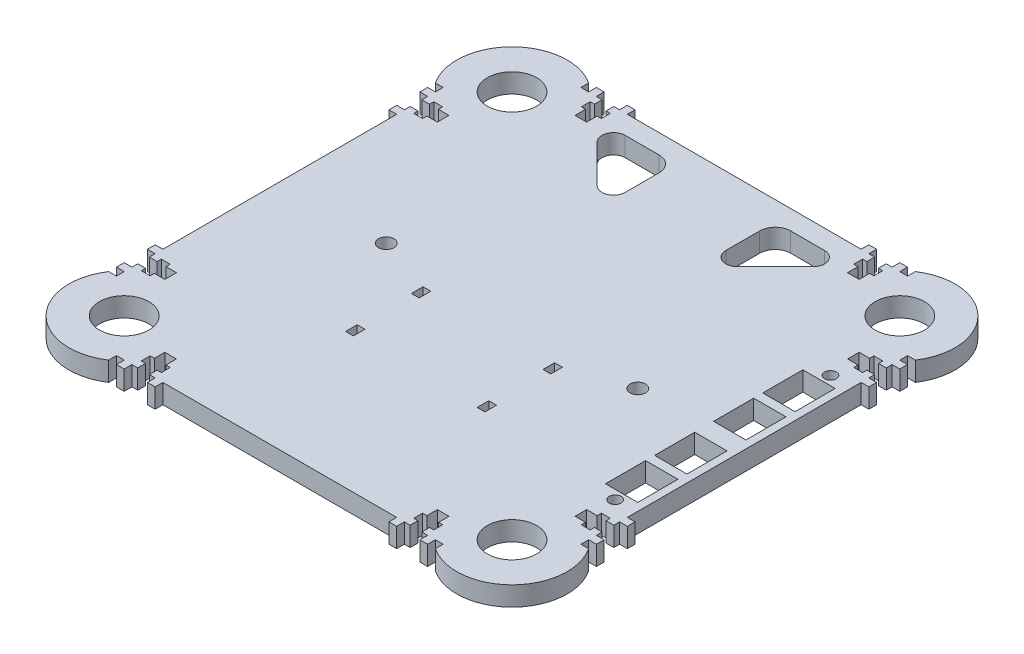
SolidWorks part; units mm, degrees
ref_plane "Front Plane" through (0, 0, 0) normal (0, 0, 1) x (1, 0, 0)
ref_plane "Top Plane" through (0, 0, 0) normal (0, 1, 0) x (1, 0, 0)
ref_plane "Right Plane" through (0, 0, 0) normal (1, 0, 0) x (0, 0, -1)
sketch "Sketch1" plane through (0, 0, 0) normal (0, 1, 0) x (1, 0, 0)
  line L1 (0, 0) -> (120, 0)
  line L2 (0, 0) -> (0, 120)
  line L3 (0, 120) -> (120, 120)
  line L4 (120, 0) -> (120, 120)
  dimension "D1" = 120
  dimension "D2" = 120
extrude "Boss-Extrude1" add sketch "Sketch1" along normal blind 5
sketch "Sketch2" plane through (0, 5, 0) normal (0, 1, 0) x (1, 0, 0)
  line L0 (60, 120) -> (60, 0) construction
  line L1 (120, 120) -> (0, 120) construction
  line L2 (0, 0) -> (120, 0) construction
  line L3 (120, 60) -> (0, 60) construction
  line L4 (120, 0) -> (120, 120) construction
  line L5 (0, 120) -> (0, 0) construction
  line L6 (60, 60) -> (120, 120) construction
  line L7 (110.1005, 110.1005) -> (120, 100.201) construction
  line L8 (110.1005, 110.1005) -> (100.201, 120) construction
  line L9 (100.201, 120) -> (120, 100.201)
  line L10 (100.201, 120) -> (114.3431, 134.1421)
  line L11 (120, 100.201) -> (134.1421, 114.3431)
  line L12 (114.3431, 134.1421) -> (134.1421, 114.3431)
  line L13 (0, 100.201) -> (-14.1421, 114.3431)
  line L14 (5.6569, 134.1421) -> (-14.1421, 114.3431)
  line L15 (19.799, 120) -> (5.6569, 134.1421)
  line L16 (19.799, 120) -> (0, 100.201)
  line L17 (19.799, 0) -> (0, 19.799)
  line L18 (19.799, 0) -> (5.6569, -14.1421)
  line L19 (5.6569, -14.1421) -> (-14.1421, 5.6569)
  line L20 (0, 19.799) -> (-14.1421, 5.6569)
  line L21 (120, 19.799) -> (134.1421, 5.6569)
  line L22 (114.3431, -14.1421) -> (134.1421, 5.6569)
  line L23 (100.201, 0) -> (114.3431, -14.1421)
  line L24 (100.201, 0) -> (120, 19.799)
  point P33 (120, 100.201)
  point P34 (100.201, 120)
  dimension "D1" = 28
  dimension "D2" = 20
extrude "Boss-Extrude3" add sketch "Sketch2" against normal blind 5
sketch "Sketch3" plane through (0, 5, 0) normal (0, 1, 0) x (1, 0, 0)
  line L0 (-4.2426, -4.2426) -> (124.2426, 124.2426) construction
  line L1 (-14.1421, 5.6569) -> (5.6569, -14.1421) construction
  line L2 (134.1421, 114.3431) -> (114.3431, 134.1421) construction
  line L3 (0, 19.799) -> (19.799, 0) construction
  line L13 (0, 60) -> (120, 60) construction
  line L14 (0, 100.201) -> (0, 19.799) construction
  line L15 (120, 19.799) -> (120, 100.201) construction
  line L16 (60, 0) -> (60, 120) construction
  line L17 (19.799, 0) -> (100.201, 0) construction
  line L18 (100.201, 120) -> (19.799, 120) construction
  circle A16 centre (9.8995, 9.8995) radius 6.375
  circle A17 centre (110.1005, 9.8995) radius 6.375
  circle A18 centre (9.8995, 110.1005) radius 6.375
  circle A19 centre (110.1005, 110.1005) radius 6.375
  point P10 (9.8995, 9.8995)
  dimension "D1" = 12.75
extrude "Cut-Extrude1" cut sketch "Sketch3" against normal blind 5
sketch "Sketch6" plane through (0, 5, 0) normal (0, 1, 0) x (1, 0, 0)
  line L0 (0, 19.799) -> (0, 17.799)
  line L1 (0, 17.799) -> (-2, 17.799)
  line L2 (0, 19.799) -> (-14.1421, 5.6569) construction
  line L3 (-2, 17.799) -> (0, 19.799)
  line L4 (0, 0) -> (124.2426, 124.2426) construction
  line L5 (134.1421, 114.3431) -> (114.3431, 134.1421) construction
  line L6 (60, 120) -> (60, 0) construction
  line L7 (100.201, 120) -> (19.799, 120) construction
  line L8 (19.799, 0) -> (100.201, 0) construction
  line L9 (0, 60) -> (120, 60) construction
  line L10 (0, 100.201) -> (0, 19.799) construction
  line L11 (120, 19.799) -> (120, 100.201) construction
  line L12 (17.799, -2) -> (19.799, 0)
  line L13 (17.799, 0) -> (17.799, -2)
  line L14 (19.799, 0) -> (17.799, 0)
  line L15 (100.201, 0) -> (102.201, 0)
  line L16 (102.201, 0) -> (102.201, -2)
  line L17 (102.201, -2) -> (100.201, 0)
  line L18 (122, 17.799) -> (120, 19.799)
  line L19 (120, 17.799) -> (122, 17.799)
  line L20 (120, 19.799) -> (120, 17.799)
  line L21 (120, 100.201) -> (120, 102.201)
  line L22 (120, 102.201) -> (122, 102.201)
  line L23 (122, 102.201) -> (120, 100.201)
  line L24 (102.201, 122) -> (100.201, 120)
  line L25 (102.201, 120) -> (102.201, 122)
  line L26 (100.201, 120) -> (102.201, 120)
  line L27 (19.799, 120) -> (17.799, 120)
  line L28 (17.799, 120) -> (17.799, 122)
  line L29 (17.799, 122) -> (19.799, 120)
  line L30 (-2, 102.201) -> (0, 100.201)
  line L31 (0, 102.201) -> (-2, 102.201)
  line L32 (0, 100.201) -> (0, 102.201)
  dimension "D1" = 2
extrude "Cut-Extrude4" cut sketch "Sketch6" against normal blind 10
sketch "Sketch8" plane through (0, 5, 0) normal (0, 1, 0) x (1, 0, 0)
  line L0 (60, 0) -> (60, 120) construction
  line L1 (17.799, 0) -> (102.201, 0) construction
  line L2 (102.201, 120) -> (17.799, 120) construction
  line L3 (0, 60) -> (120, 60) construction
  line L4 (0, 102.201) -> (0, 17.799) construction
  line L5 (120, 17.799) -> (120, 102.201) construction
  line L6 (-4.2426, 124.2426) -> (124.2426, -4.2426) construction
  line L7 (5.6569, 134.1421) -> (-14.1421, 114.3431) construction
  line L8 (114.3431, -14.1421) -> (134.1421, 5.6569) construction
  line L9 (24.799, 0) -> (24.799, 7) construction
  line L10 (23.299, 2) -> (23.299, 0)
  line L11 (26.299, 7) -> (23.299, 7)
  line L12 (26.299, 7) -> (26.299, 4.3)
  line L13 (26.299, 0) -> (23.299, 0)
  line L14 (23.299, 7) -> (23.299, 4.3)
  line L15 (26.299, 7) -> (23.299, 0) construction
  line L16 (26.299, 0) -> (23.299, 7) construction
  line L17 (23.299, 2) -> (22.199, 2)
  line L19 (23.299, 4.3) -> (22.199, 4.3)
  line L20 (22.199, 2) -> (22.199, 4.3)
  line L21 (26.299, 4.3) -> (27.399, 4.3)
  line L22 (27.399, 2) -> (27.399, 4.3)
  line L23 (26.299, 2) -> (27.399, 2)
  line L24 (26.299, 2) -> (26.299, 0)
  line L25 (17.799, 0) -> (17.799, -2) construction
  line L26 (93.701, 0) -> (96.701, 7) construction
  line L27 (93.701, 7) -> (96.701, 0) construction
  line L28 (95.201, 0) -> (95.201, 7) construction
  line L29 (93.701, 2) -> (93.701, 0)
  line L30 (93.701, 2) -> (92.601, 2)
  line L31 (92.601, 2) -> (92.601, 4.3)
  line L32 (93.701, 4.3) -> (92.601, 4.3)
  line L33 (97.801, 2) -> (97.801, 4.3)
  line L34 (96.701, 4.3) -> (97.801, 4.3)
  line L35 (96.701, 2) -> (97.801, 2)
  line L36 (96.701, 7) -> (96.701, 4.3)
  line L37 (93.701, 0) -> (96.701, 0)
  line L38 (93.701, 7) -> (93.701, 4.3)
  line L39 (93.701, 7) -> (96.701, 7)
  line L40 (96.701, 2) -> (96.701, 0)
  line L41 (95.201, 120) -> (95.201, 113) construction
  line L42 (93.701, 113) -> (96.701, 120) construction
  line L43 (93.701, 120) -> (96.701, 113) construction
  line L44 (26.299, 120) -> (23.299, 113) construction
  line L45 (26.299, 113) -> (23.299, 120) construction
  line L46 (24.799, 120) -> (24.799, 113) construction
  line L47 (96.701, 118) -> (96.701, 120)
  line L48 (93.701, 113) -> (96.701, 113)
  line L49 (93.701, 113) -> (93.701, 115.7)
  line L50 (93.701, 120) -> (96.701, 120)
  line L51 (96.701, 113) -> (96.701, 115.7)
  line L52 (96.701, 118) -> (97.801, 118)
  line L53 (96.701, 115.7) -> (97.801, 115.7)
  line L54 (97.801, 118) -> (97.801, 115.7)
  line L55 (93.701, 115.7) -> (92.601, 115.7)
  line L56 (92.601, 118) -> (92.601, 115.7)
  line L57 (93.701, 118) -> (92.601, 118)
  line L58 (93.701, 118) -> (93.701, 120)
  line L59 (26.299, 118) -> (26.299, 120)
  line L60 (26.299, 118) -> (27.399, 118)
  line L61 (27.399, 118) -> (27.399, 115.7)
  line L62 (26.299, 115.7) -> (27.399, 115.7)
  line L63 (22.199, 118) -> (22.199, 115.7)
  line L64 (23.299, 115.7) -> (22.199, 115.7)
  line L65 (23.299, 118) -> (22.199, 118)
  line L66 (23.299, 113) -> (23.299, 115.7)
  line L67 (26.299, 120) -> (23.299, 120)
  line L68 (26.299, 113) -> (26.299, 115.7)
  line L69 (26.299, 113) -> (23.299, 113)
  line L70 (23.299, 118) -> (23.299, 120)
  line L71 (0, 95.201) -> (7, 95.201) construction
  line L72 (7, 93.701) -> (0, 96.701) construction
  line L73 (0, 93.701) -> (7, 96.701) construction
  line L74 (0, 26.299) -> (7, 23.299) construction
  line L75 (7, 26.299) -> (0, 23.299) construction
  line L76 (0, 24.799) -> (7, 24.799) construction
  line L77 (120, 24.799) -> (113, 24.799) construction
  line L78 (113, 26.299) -> (120, 23.299) construction
  line L79 (120, 26.299) -> (113, 23.299) construction
  line L80 (120, 93.701) -> (113, 96.701) construction
  line L81 (113, 93.701) -> (120, 96.701) construction
  line L82 (120, 95.201) -> (113, 95.201) construction
  line L83 (2, 96.701) -> (0, 96.701)
  line L84 (7, 93.701) -> (7, 96.701)
  line L85 (7, 93.701) -> (4.3, 93.701)
  line L86 (0, 93.701) -> (0, 96.701)
  line L87 (7, 96.701) -> (4.3, 96.701)
  line L88 (2, 96.701) -> (2, 97.801)
  line L89 (4.3, 96.701) -> (4.3, 97.801)
  line L90 (2, 97.801) -> (4.3, 97.801)
  line L91 (4.3, 93.701) -> (4.3, 92.601)
  line L92 (2, 92.601) -> (4.3, 92.601)
  line L93 (2, 93.701) -> (2, 92.601)
  line L94 (2, 93.701) -> (0, 93.701)
  line L95 (2, 26.299) -> (0, 26.299)
  line L96 (2, 26.299) -> (2, 27.399)
  line L97 (2, 27.399) -> (4.3, 27.399)
  line L98 (4.3, 26.299) -> (4.3, 27.399)
  line L99 (2, 22.199) -> (4.3, 22.199)
  line L100 (4.3, 23.299) -> (4.3, 22.199)
  line L101 (2, 23.299) -> (2, 22.199)
  line L102 (7, 23.299) -> (4.3, 23.299)
  line L103 (0, 26.299) -> (0, 23.299)
  line L104 (7, 26.299) -> (4.3, 26.299)
  line L105 (7, 26.299) -> (7, 23.299)
  line L106 (2, 23.299) -> (0, 23.299)
  line L107 (118, 23.299) -> (120, 23.299)
  line L108 (113, 26.299) -> (113, 23.299)
  line L109 (113, 26.299) -> (115.7, 26.299)
  line L110 (120, 26.299) -> (120, 23.299)
  line L111 (113, 23.299) -> (115.7, 23.299)
  line L112 (118, 23.299) -> (118, 22.199)
  line L113 (115.7, 23.299) -> (115.7, 22.199)
  line L114 (118, 22.199) -> (115.7, 22.199)
  line L115 (115.7, 26.299) -> (115.7, 27.399)
  line L116 (118, 27.399) -> (115.7, 27.399)
  line L117 (118, 26.299) -> (118, 27.399)
  line L118 (118, 26.299) -> (120, 26.299)
  line L119 (118, 93.701) -> (120, 93.701)
  line L120 (118, 93.701) -> (118, 92.601)
  line L121 (118, 92.601) -> (115.7, 92.601)
  line L122 (115.7, 93.701) -> (115.7, 92.601)
  line L123 (118, 97.801) -> (115.7, 97.801)
  line L124 (115.7, 96.701) -> (115.7, 97.801)
  line L125 (118, 96.701) -> (118, 97.801)
  line L126 (113, 96.701) -> (115.7, 96.701)
  line L127 (120, 93.701) -> (120, 96.701)
  line L128 (113, 93.701) -> (115.7, 93.701)
  line L129 (113, 93.701) -> (113, 96.701)
  line L130 (118, 96.701) -> (120, 96.701)
  point P20 (24.799, 3.5)
  point P49 (95.201, 3.5)
  point P78 (95.201, 116.5)
  point P79 (24.799, 116.5)
  point P136 (3.5, 95.201)
  point P137 (3.5, 24.799)
  point P138 (116.5, 24.799)
  point P139 (116.5, 95.201)
  dimension "D1" = 2
  dimension "D2" = 2.3
  dimension "D3" = 7
  dimension "D4" = 7
  dimension "D5" = 3
  dimension "D6" = 1.1
extrude "Cut-Extrude6" cut sketch "Sketch8" against normal blind 10
sketch "Sketch9" plane through (0, 5, 0) normal (0, 1, 0) x (1, 0, 0)
  line L0 (7, 95.201) -> (-3.557, 95.201) construction
  line L1 (7, 93.701) -> (7, 96.701) construction
  line L2 (-4.2426, 124.2426) -> (124.2426, -4.2426) construction
  line L3 (5.6569, 134.1421) -> (-14.1421, 114.3431) construction
  line L4 (114.3431, -14.1421) -> (134.1421, 5.6569) construction
  line L5 (60, 0) -> (60, 120) construction
  line L6 (26.299, 0) -> (93.701, 0) construction
  line L7 (93.701, 120) -> (26.299, 120) construction
  line L8 (0, 60) -> (120, 60) construction
  line L9 (0, 93.701) -> (0, 26.299) construction
  line L10 (120, 26.299) -> (120, 93.701) construction
  line L11 (0, 102.201) -> (0, 96.701) construction
  line L12 (0, 98.201) -> (-2, 98.201)
  line L13 (0, 98.201) -> (0, 100.201)
  line L14 (0, 100.201) -> (-2, 100.201)
  line L15 (-2, 98.201) -> (-2, 100.201)
  line L16 (0, 90.201) -> (-2, 90.201)
  line L17 (-2, 92.201) -> (-2, 90.201)
  line L18 (0, 92.201) -> (-2, 92.201)
  line L19 (0, 92.201) -> (0, 90.201)
  line L20 (19.799, 120) -> (19.799, 122)
  line L21 (21.799, 122) -> (19.799, 122)
  line L22 (21.799, 120) -> (21.799, 122)
  line L23 (21.799, 120) -> (19.799, 120)
  line L24 (27.799, 120) -> (29.799, 120)
  line L25 (27.799, 120) -> (27.799, 122)
  line L26 (27.799, 122) -> (29.799, 122)
  line L27 (29.799, 120) -> (29.799, 122)
  line L28 (92.201, 120) -> (92.201, 122)
  line L29 (92.201, 122) -> (90.201, 122)
  line L30 (90.201, 120) -> (90.201, 122)
  line L31 (92.201, 120) -> (90.201, 120)
  line L32 (98.201, 120) -> (100.201, 120)
  line L33 (98.201, 120) -> (98.201, 122)
  line L34 (98.201, 122) -> (100.201, 122)
  line L35 (100.201, 120) -> (100.201, 122)
  line L36 (120, 100.201) -> (122, 100.201)
  line L37 (122, 98.201) -> (122, 100.201)
  line L38 (120, 98.201) -> (122, 98.201)
  line L39 (120, 98.201) -> (120, 100.201)
  line L40 (120, 92.201) -> (120, 90.201)
  line L41 (120, 92.201) -> (122, 92.201)
  line L42 (122, 92.201) -> (122, 90.201)
  line L43 (120, 90.201) -> (122, 90.201)
  line L44 (120, 27.799) -> (122, 27.799)
  line L45 (122, 27.799) -> (122, 29.799)
  line L46 (120, 29.799) -> (122, 29.799)
  line L47 (120, 27.799) -> (120, 29.799)
  line L48 (120, 21.799) -> (120, 19.799)
  line L49 (120, 21.799) -> (122, 21.799)
  line L50 (122, 21.799) -> (122, 19.799)
  line L51 (120, 19.799) -> (122, 19.799)
  line L52 (98.201, 0) -> (98.201, -2)
  line L53 (98.201, -2) -> (100.201, -2)
  line L54 (100.201, 0) -> (100.201, -2)
  line L55 (98.201, 0) -> (100.201, 0)
  line L56 (92.201, 0) -> (90.201, 0)
  line L57 (90.201, 0) -> (90.201, -2)
  line L58 (92.201, -2) -> (90.201, -2)
  line L59 (92.201, 0) -> (92.201, -2)
  line L60 (27.799, 0) -> (27.799, -2)
  line L61 (27.799, -2) -> (29.799, -2)
  line L62 (29.799, 0) -> (29.799, -2)
  line L63 (27.799, 0) -> (29.799, 0)
  line L64 (21.799, 0) -> (19.799, 0)
  line L65 (21.799, 0) -> (21.799, -2)
  line L66 (21.799, -2) -> (19.799, -2)
  line L67 (19.799, 0) -> (19.799, -2)
  line L68 (0, 19.799) -> (-2, 19.799)
  line L69 (-2, 21.799) -> (-2, 19.799)
  line L70 (0, 21.799) -> (-2, 21.799)
  line L71 (0, 21.799) -> (0, 19.799)
  line L72 (0, 27.799) -> (0, 29.799)
  line L73 (0, 27.799) -> (-2, 27.799)
  line L74 (-2, 27.799) -> (-2, 29.799)
  line L75 (0, 29.799) -> (-2, 29.799)
  dimension "D1" = 2
  dimension "D2" = 2
  dimension "D3" = 3
extrude "Boss-Extrude4" add sketch "Sketch9" against normal blind 5
sketch "Sketch10" plane through (0, 5, 0) normal (0, 1, 0) x (1, 0, 0)
  line L0 (-4.2426, 124.2426) -> (124.2426, -4.2426) construction
  line L1 (5.6569, 134.1421) -> (-14.1421, 114.3431) construction
  line L2 (114.3431, -14.1421) -> (134.1421, 5.6569) construction
  line L3 (9.8995, 110.1005) -> (-2, 98.201) construction
  line L4 (0, 102.201) -> (-2, 102.201) construction
  line L5 (-2, 102.201) -> (-14.1421, 114.3431)
  line L6 (-14.1421, 114.3431) -> (5.6569, 134.1421)
  line L7 (5.6569, 134.1421) -> (17.799, 122)
  line L8 (60, 120) -> (60, 0) construction
  line L9 (90.201, 120) -> (29.799, 120) construction
  line L10 (29.799, 0) -> (90.201, 0) construction
  line L11 (0, 60) -> (120, 60) construction
  line L12 (0, 90.201) -> (0, 29.799) construction
  line L13 (120, 29.799) -> (120, 90.201) construction
  line L14 (-14.1421, 5.6569) -> (5.6569, -14.1421)
  line L15 (-2, 17.799) -> (-14.1421, 5.6569)
  line L16 (5.6569, -14.1421) -> (17.799, -2)
  line L17 (122, 17.799) -> (134.1421, 5.6569)
  line L18 (114.3431, -14.1421) -> (102.201, -2)
  line L19 (134.1421, 5.6569) -> (114.3431, -14.1421)
  line L20 (134.1421, 114.3431) -> (114.3431, 134.1421)
  line L21 (122, 102.201) -> (134.1421, 114.3431)
  line L22 (114.3431, 134.1421) -> (102.201, 122)
  arc A0 (17.799, 122) -> (-2, 102.201) centre (9.8995, 110.1005) ccw
  arc A1 (17.799, -2) -> (-2, 17.799) centre (9.8995, 9.8995) cw
  arc A2 (102.201, -2) -> (122, 17.799) centre (110.1005, 9.8995) ccw
  arc A3 (102.201, 122) -> (122, 102.201) centre (110.1005, 110.1005) cw
extrude "Cut-Extrude7" cut sketch "Sketch10" against normal blind 10
sketch "Sketch11" plane through (0, 5, 0) normal (0, 1, 0) x (1, 0, 0)
  line L0 (60, 120) -> (60, 0) construction
  line L1 (90.201, 120) -> (29.799, 120) construction
  line L2 (29.799, 0) -> (90.201, 0) construction
  line L3 (60, 68) -> (70, 68) construction
  line L12 (60, 28) -> (76, 28) construction
  line L13 (76, 28) -> (76, 52) construction
  line L14 (76, 45) -> (60, 45) construction
  line L15 (76, 52) -> (78, 52)
  line L16 (76, 52) -> (76, 55)
  line L17 (76, 55) -> (78, 55)
  line L18 (78, 52) -> (78, 55)
  line L19 (76, 35) -> (78, 35)
  line L20 (78, 38) -> (78, 35)
  line L21 (76, 38) -> (78, 38)
  line L22 (76, 38) -> (76, 35)
  line L23 (44, 38) -> (44, 35)
  line L24 (44, 38) -> (42, 38)
  line L25 (42, 38) -> (42, 35)
  line L26 (44, 35) -> (42, 35)
  line L27 (44, 55) -> (42, 55)
  line L28 (42, 52) -> (42, 55)
  line L29 (44, 52) -> (42, 52)
  line L30 (44, 52) -> (44, 55)
  dimension "D1" = 2
  dimension "D2" = 3
  dimension "D6" = 10
  dimension "D7" = 17
  dimension "D8" = 16
extrude "Cut-Extrude9" cut sketch "Sketch11" against normal blind 5
sketch "Sketch13" plane through (0, 5, 0) normal (0, 1, 0) x (1, 0, 0)
  line L0 (60, 120) -> (60, 0) construction
  line L1 (90.201, 120) -> (29.799, 120) construction
  line L2 (29.799, 0) -> (90.201, 0) construction
  line L3 (60, 60) -> (92.5, 60) construction
  circle A0 centre (92.5, 60) radius 2
  circle A1 centre (27.5, 60) radius 2
  dimension "D1" = 4
  dimension "D2" = 32.5
extrude "Cut-Extrude10" cut sketch "Sketch13" against normal blind 5
sketch "Sketch14" plane through (0, 5, 0) normal (0, 1, 0) x (1, 0, 0)
  line L0 (0, 60) -> (120, 60) construction
  line L1 (0, 90.201) -> (0, 29.799) construction
  line L2 (120, 29.799) -> (120, 90.201) construction
  line L3 (0, 97) -> (120, 97) construction
  line L4 (60, 97) -> (60, 105) construction
  line L5 (60, 105) -> (37, 105) construction
  line L6 (47, 95) -> (27, 115)
  line L7 (27, 115) -> (47, 115)
  line L8 (47, 115) -> (47, 95)
  line L9 (93, 115) -> (73, 115)
  line L10 (73, 95) -> (93, 115)
  line L11 (73, 115) -> (73, 95)
  line L12 (90.201, 120) -> (29.799, 120) construction
  point P14 (37, 105)
  dimension "D4" = 20
  dimension "D5" = 5
  dimension "D1" = 37
  dimension "D2" = 23
extrude "Cut-Extrude11" cut sketch "Sketch14" against normal blind 10
fillet "Fillet1" radius 3 4 edges at (93, 2.5, -115) (73, 2.5, -95) (47, 2.5, -95) (27, 2.5, -115)
fillet "Fillet2" radius 4 2 edges at (47, 2.5, -115) (73, 2.5, -115)
sketch "Sketch17" plane through (191.572, 5, 58.0177) normal (0, 1, 0) x (0, 0, -1)
  line L0 (90.2027, 99.702) -> (90.2027, 96.402) construction
  line L1 (93.4447, 86.752) -> (142.5907, 86.752) construction
  line L2 (118.0177, 86.752) -> (118.0177, 71.572) construction
  line L3 (118.0177, 110.4423) -> (118.0177, 77.747) construction
  line L4 (118.0177, 77.747) -> (125.6377, 77.747) construction
  line L5 (125.6377, 77.747) -> (138.3377, 77.747) construction
  line L6 (130.8177, 81.922) -> (120.4577, 81.922)
  line L7 (130.8177, 81.922) -> (130.8177, 73.572)
  line L8 (130.8177, 73.572) -> (120.4577, 73.572)
  line L9 (120.4577, 81.922) -> (120.4577, 73.572)
  line L10 (130.8177, 81.922) -> (120.4577, 73.572) construction
  line L11 (130.8177, 73.572) -> (120.4577, 81.922) construction
  line L12 (92.5177, 81.922) -> (102.8777, 81.922)
  line L13 (143.5177, 73.572) -> (133.1577, 73.572)
  line L14 (143.5177, 73.572) -> (143.5177, 81.922)
  line L15 (143.5177, 81.922) -> (133.1577, 81.922)
  line L16 (133.1577, 73.572) -> (133.1577, 81.922)
  line L17 (143.5177, 73.572) -> (133.1577, 81.922) construction
  line L18 (143.5177, 81.922) -> (133.1577, 73.572) construction
  line L19 (102.8777, 73.572) -> (102.8777, 81.922)
  line L20 (92.5177, 73.572) -> (102.8777, 73.572)
  line L21 (92.5177, 73.572) -> (92.5177, 81.922)
  line L22 (105.2177, 73.572) -> (115.5777, 73.572)
  line L23 (115.5777, 81.922) -> (115.5777, 73.572)
  line L24 (105.2177, 81.922) -> (115.5777, 81.922)
  line L25 (105.2177, 81.922) -> (105.2177, 73.572)
  line L26 (90.2027, 99.702) -> (118.0177, 86.752) construction
  line L27 (87.8167, 71.572) -> (148.2187, 71.572) construction
  circle A0 centre (90.2027, 96.402) radius 1.524
  circle A1 centre (90.2027, 77.102) radius 1.524
  circle A2 centre (145.8327, 77.102) radius 1.524
  circle A3 centre (145.8327, 96.402) radius 1.524
  point P33 (110.3977, 73.572)
  point P34 (125.6377, 73.572)
  point P35 (0, 0)
  point P36 (118.1529, 16.8391)
  point P37 (0, 0)
  point P38 (0, 0)
  point P41 (118.0177, 71.572)
  point P42 (118.0177, 85.7192)
  dimension "D2" = 3.048
  dimension "D1" = 3.3
  dimension "D3" = 15.24
  dimension "D4" = 10.36
  dimension "D5" = 12.7
  dimension "D6" = 8.35
  dimension "D7" = 30.6819
  dimension "D8" = 24.966
  dimension "D9" = 4.83
  dimension "D10" = 2
extrude "Cut-Extrude12" cut sketch "Sketch17" against normal blind 10
sketch "Sketch18" plane through (0, 5, 0) normal (0, 1, 0) x (1, 0, 0)
  circle A0 centre (95.17, 87.815) radius 1.524
  circle A1 centre (95.17, 32.185) radius 1.524
extrude "Boss-Extrude6" add sketch "Sketch18" against normal blind 5
